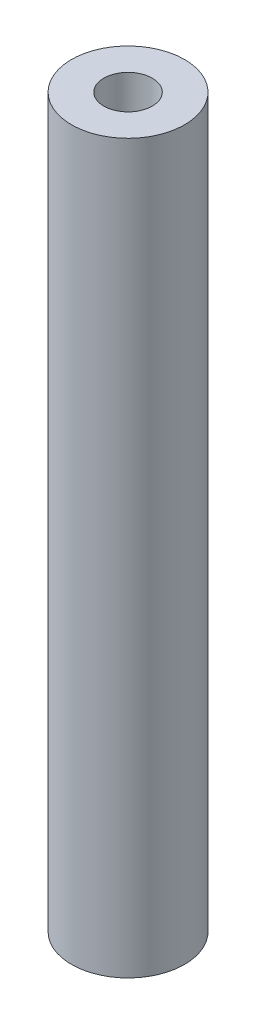
SolidWorks part; units mm, degrees
ref_plane "Front Plane" through (0, 0, 0) normal (0, 0, 1) x (1, 0, 0)
ref_plane "Top Plane" through (0, 0, 0) normal (0, 1, 0) x (1, 0, 0)
ref_plane "Right Plane" through (0, 0, 0) normal (1, 0, 0) x (0, 0, -1)
sketch "Sketch1" plane through (0, 0, 0) normal (0, 1, 0) x (1, 0, 0)
  circle A0 centre (0, 0) radius 7
  circle A1 centre (0, 0) radius 3
  dimension "D1" = 6
  dimension "D2" = 14
extrude "Boss-Extrude1" add sketch "Sketch1" along normal blind 90
